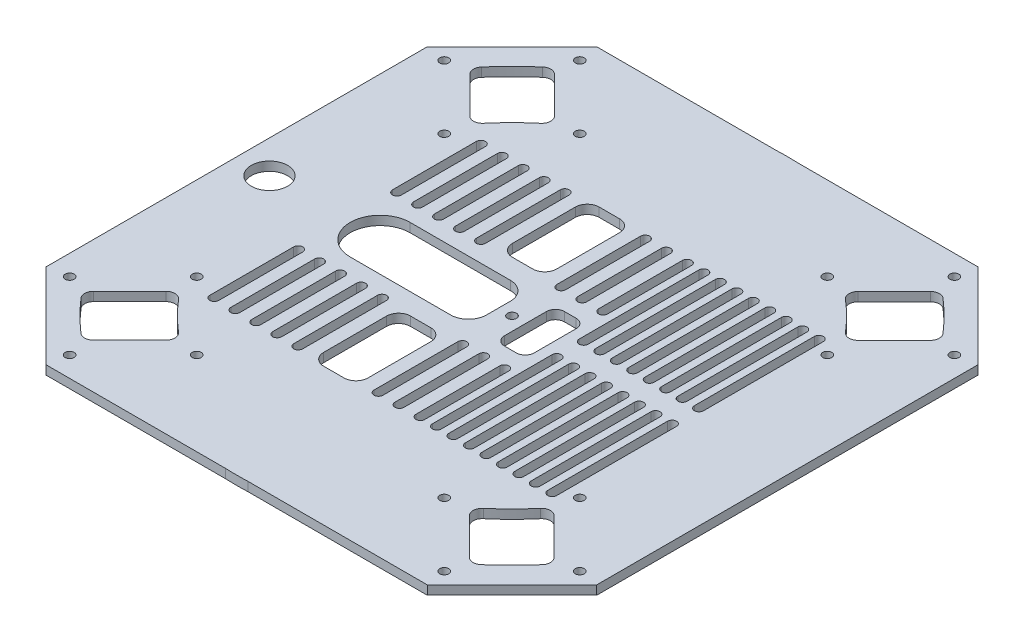
SolidWorks part; units mm, degrees
material "Thornel Mat VMA"
ref_plane "前视基准面" through (0, 0, 0) normal (0, 0, 1) x (1, 0, 0)
ref_plane "上视基准面" through (0, 0, 0) normal (0, 1, 0) x (1, 0, 0)
ref_plane "右视基准面" through (0, 0, 0) normal (1, 0, 0) x (0, 0, -1)
sketch "草图1" plane through (0, 0, 0) normal (0, 1, 0) x (1, 0, 0)
  line L0 (-63.6396, 91.9239) -> (-91.9239, 63.6396)
  line L1 (63.6396, 91.9239) -> (-63.6396, 91.9239)
  line L2 (91.9239, 63.6396) -> (91.9239, -63.6396)
  line L3 (63.6396, -91.9239) -> (-63.6396, -91.9239)
  line L4 (-91.9239, 63.6396) -> (-91.9239, -63.6396)
  line L5 (91.9239, 91.9239) -> (-91.9239, -91.9239) construction
  line L6 (91.9239, -91.9239) -> (-91.9239, 91.9239) construction
  line L7 (91.9239, -63.6396) -> (63.6396, -91.9239)
  line L8 (-91.9239, -63.6396) -> (-63.6396, -91.9239)
  line L9 (63.6396, 91.9239) -> (91.9239, 63.6396)
  line L10 (-91.9239, 91.9239) -> (-91.9239, -91.9239) construction
  line L11 (-91.9239, -91.9239) -> (91.9239, -91.9239) construction
  line L12 (91.9239, -91.9239) -> (91.9239, 91.9239) construction
  line L13 (91.9239, 91.9239) -> (-91.9239, 91.9239) construction
  point P0 (0, 0)
  dimension "D1" = 220
  dimension "D2" = 40
extrude "凸台-拉伸1" add sketch "草图1" along normal blind 3
sketch "草图15" plane through (0, 3, 0) normal (0, 1, 0) x (1, 0, 0)
  line L1 (-40.3412, 82.6837) -> (-31.9185, 62.6852)
  line L2 (44.6358, 80.4465) -> (36.2732, 60.2701)
  line L3 (-42.4295, -81.6317) -> (-34.5316, -61.2845)
  line L4 (41.391, -82.1632) -> (34.5498, -61.2743)
  arc A0 (-42.4295, -81.6317) -> (41.391, -82.1632) centre (0, 0) ccw
  arc A2 (-34.5316, -61.2845) -> (34.5498, -61.2743) centre (0, 0) ccw
  arc A3 (36.2732, 60.2701) -> (-31.9185, 62.6852) centre (0, 0) ccw
  arc A4 (44.6358, 80.4465) -> (-40.3412, 82.6837) centre (0, 0) ccw
  dimension "D1" = 92
extrude "凸台-拉伸3" add sketch "草图15" against normal up to surface (3 mm away) up to face at (0, 0, 0)
sketch "草图18" plane through (0, 3, 0) normal (0, 1, 0) x (1, 0, 0)
  line L0 (-44.0207, 0) -> (12.6253, 0) construction
  line L1 (-44.0207, 10) -> (-10.5, 10)
  line L2 (-44.0207, -10) -> (-10.5, -10)
  line L3 (-54.0207, 0) -> (-91.9239, 0) construction
  line L4 (-91.9239, 63.6396) -> (-91.9239, -63.6396) construction
  line L5 (-4.5, -10) -> (4.5, -10) construction
  line L6 (-4.5, 4) -> (-4.5, -4)
  line L9 (-4.5, 10) -> (4.5, -10) construction
  line L10 (-4.5, -10) -> (4.5, 10) construction
  line L11 (-4.5, 10) -> (4.5, 10) construction
  arc A0 (-44.0207, 10) -> (-44.0207, -10) centre (-44.0207, 0) ccw
  arc A3 (-10.5, 10) -> (-4.5, 4) centre (-10.5, 4) cw
  arc A8 (-4.5, -4) -> (-10.5, -10) centre (-10.5, -4) cw
  circle A9 centre (0, 0) radius 1.5
  point P3 (0, 0)
  point P14 (-54.0207, 0)
  point P15 (0, 0)
  dimension "D5" = 6
extrude "切除-拉伸5" cut sketch "草图18" against normal through all both and the other way through all
sketch "草图20" plane through (0, 0, 0) normal (0, -1, 0) x (1, 0, 0)
  line L0 (-45.8783, 0) -> (57.9239, 0) construction
  line L1 (57.9239, 44.5) -> (57.9239, 4.5) construction
  line L2 (59.4239, 44.5) -> (59.4239, 4.5)
  line L3 (56.4239, 44.5) -> (56.4239, 4.5)
  line L4 (57.9239, -44.5) -> (57.9239, -4.5) construction
  line L5 (59.4239, -44.5) -> (59.4239, -4.5)
  line L6 (56.4239, -44.5) -> (56.4239, -4.5)
  line L7 (52.4239, 44.5) -> (52.4239, 4.5) construction
  line L8 (53.9239, 44.5) -> (53.9239, 4.5)
  line L9 (50.9239, 44.5) -> (50.9239, 4.5)
  line L10 (52.4239, -44.5) -> (52.4239, -4.5) construction
  line L11 (53.9239, -44.5) -> (53.9239, -4.5)
  line L12 (50.9239, -44.5) -> (50.9239, -4.5)
  line L13 (46.9239, 44.5) -> (46.9239, 4.5) construction
  line L14 (48.4239, 44.5) -> (48.4239, 4.5)
  line L15 (45.4239, 44.5) -> (45.4239, 4.5)
  line L16 (46.9239, -44.5) -> (46.9239, -4.5) construction
  line L17 (48.4239, -44.5) -> (48.4239, -4.5)
  line L18 (45.4239, -44.5) -> (45.4239, -4.5)
  line L19 (41.4239, 44.5) -> (41.4239, 4.5) construction
  line L20 (42.9239, 44.5) -> (42.9239, 4.5)
  line L21 (39.9239, 44.5) -> (39.9239, 4.5)
  line L22 (41.4239, -44.5) -> (41.4239, -4.5) construction
  line L23 (42.9239, -44.5) -> (42.9239, -4.5)
  line L24 (39.9239, -44.5) -> (39.9239, -4.5)
  line L25 (35.9239, 44.5) -> (35.9239, 4.5) construction
  line L26 (37.4239, 44.5) -> (37.4239, 4.5)
  line L27 (34.4239, 44.5) -> (34.4239, 4.5)
  line L28 (35.9239, -44.5) -> (35.9239, -4.5) construction
  line L29 (37.4239, -44.5) -> (37.4239, -4.5)
  line L30 (34.4239, -44.5) -> (34.4239, -4.5)
  line L31 (30.4239, 44.5) -> (30.4239, 4.5) construction
  line L32 (31.9239, 44.5) -> (31.9239, 4.5)
  line L33 (28.9239, 44.5) -> (28.9239, 4.5)
  line L34 (30.4239, -44.5) -> (30.4239, -4.5) construction
  line L35 (31.9239, -44.5) -> (31.9239, -4.5)
  line L36 (28.9239, -44.5) -> (28.9239, -4.5)
  line L37 (24.9239, 44.5) -> (24.9239, 4.5) construction
  line L38 (26.4239, 44.5) -> (26.4239, 4.5)
  line L39 (23.4239, 44.5) -> (23.4239, 4.5)
  line L40 (24.9239, -44.5) -> (24.9239, -4.5) construction
  line L41 (26.4239, -44.5) -> (26.4239, -4.5)
  line L42 (23.4239, -44.5) -> (23.4239, -4.5)
  line L43 (19.4239, 44.5) -> (19.4239, 4.5) construction
  line L44 (20.9239, 44.5) -> (20.9239, 4.5)
  line L45 (17.9239, 44.5) -> (17.9239, 4.5)
  line L46 (19.4239, -44.5) -> (19.4239, -4.5) construction
  line L47 (20.9239, -44.5) -> (20.9239, -4.5)
  line L48 (17.9239, -44.5) -> (17.9239, -4.5)
  line L49 (91.9239, 63.6396) -> (91.9239, -63.6396) construction
  line L358 (13.9239, -44.5) -> (13.9239, -4.5) construction
  line L359 (12.4239, -44.5) -> (12.4239, -4.5) [skipped]
  line L360 (15.4239, -44.5) -> (15.4239, -4.5) [skipped]
  line L361 (13.9239, 44.5) -> (13.9239, 4.5) construction
  line L362 (15.4239, 44.5) -> (15.4239, 4.5) [skipped]
  line L363 (12.4239, 44.5) -> (12.4239, 4.5) [skipped]
  line L364 (13.9239, -44.5) -> (13.9239, -4.5) construction
  line L365 (12.4239, -44.5) -> (12.4239, -4.5) [skipped]
  line L366 (15.4239, -44.5) -> (15.4239, -4.5) [skipped]
  line L367 (13.9239, 44.5) -> (13.9239, 4.5) construction
  line L368 (15.4239, 44.5) -> (15.4239, 4.5) [skipped]
  line L369 (12.4239, 44.5) -> (12.4239, 4.5) [skipped]
  arc A0 (59.4239, 44.5) -> (56.4239, 44.5) centre (57.9239, 44.5) ccw
  arc A1 (56.4239, 4.5) -> (59.4239, 4.5) centre (57.9239, 4.5) ccw
  arc A2 (59.4239, -44.5) -> (56.4239, -44.5) centre (57.9239, -44.5) cw
  arc A3 (56.4239, -4.5) -> (59.4239, -4.5) centre (57.9239, -4.5) cw
  arc A4 (53.9239, 44.5) -> (50.9239, 44.5) centre (52.4239, 44.5) ccw
  arc A5 (50.9239, 4.5) -> (53.9239, 4.5) centre (52.4239, 4.5) ccw
  arc A6 (53.9239, -44.5) -> (50.9239, -44.5) centre (52.4239, -44.5) cw
  arc A7 (50.9239, -4.5) -> (53.9239, -4.5) centre (52.4239, -4.5) cw
  arc A8 (48.4239, 44.5) -> (45.4239, 44.5) centre (46.9239, 44.5) ccw
  arc A9 (45.4239, 4.5) -> (48.4239, 4.5) centre (46.9239, 4.5) ccw
  arc A10 (48.4239, -44.5) -> (45.4239, -44.5) centre (46.9239, -44.5) cw
  arc A11 (45.4239, -4.5) -> (48.4239, -4.5) centre (46.9239, -4.5) cw
  arc A12 (42.9239, 44.5) -> (39.9239, 44.5) centre (41.4239, 44.5) ccw
  arc A13 (39.9239, 4.5) -> (42.9239, 4.5) centre (41.4239, 4.5) ccw
  arc A14 (42.9239, -44.5) -> (39.9239, -44.5) centre (41.4239, -44.5) cw
  arc A15 (39.9239, -4.5) -> (42.9239, -4.5) centre (41.4239, -4.5) cw
  arc A16 (37.4239, 44.5) -> (34.4239, 44.5) centre (35.9239, 44.5) ccw
  arc A17 (34.4239, 4.5) -> (37.4239, 4.5) centre (35.9239, 4.5) ccw
  arc A18 (37.4239, -44.5) -> (34.4239, -44.5) centre (35.9239, -44.5) cw
  arc A19 (34.4239, -4.5) -> (37.4239, -4.5) centre (35.9239, -4.5) cw
  arc A20 (31.9239, 44.5) -> (28.9239, 44.5) centre (30.4239, 44.5) ccw
  arc A21 (28.9239, 4.5) -> (31.9239, 4.5) centre (30.4239, 4.5) ccw
  arc A22 (31.9239, -44.5) -> (28.9239, -44.5) centre (30.4239, -44.5) cw
  arc A23 (28.9239, -4.5) -> (31.9239, -4.5) centre (30.4239, -4.5) cw
  arc A24 (26.4239, 44.5) -> (23.4239, 44.5) centre (24.9239, 44.5) ccw
  arc A25 (23.4239, 4.5) -> (26.4239, 4.5) centre (24.9239, 4.5) ccw
  arc A26 (26.4239, -44.5) -> (23.4239, -44.5) centre (24.9239, -44.5) cw
  arc A27 (23.4239, -4.5) -> (26.4239, -4.5) centre (24.9239, -4.5) cw
  arc A28 (20.9239, 44.5) -> (17.9239, 44.5) centre (19.4239, 44.5) ccw
  arc A29 (17.9239, 4.5) -> (20.9239, 4.5) centre (19.4239, 4.5) ccw
  arc A30 (20.9239, -44.5) -> (17.9239, -44.5) centre (19.4239, -44.5) cw
  arc A31 (17.9239, -4.5) -> (20.9239, -4.5) centre (19.4239, -4.5) cw
  arc A242 (12.4239, -44.5) -> (15.4239, -44.5) centre (13.9239, -44.5) ccw [skipped]
  arc A243 (15.4239, -4.5) -> (12.4239, -4.5) centre (13.9239, -4.5) ccw [skipped]
  arc A244 (15.4239, 44.5) -> (12.4239, 44.5) centre (13.9239, 44.5) ccw [skipped]
  arc A245 (12.4239, 4.5) -> (15.4239, 4.5) centre (13.9239, 4.5) ccw [skipped]
  point P5 (57.9239, 24.5)
  point P11 (57.9239, 3)
  point P13 (57.9239, -24.5)
  point P18 (57.9239, -3)
  point P19 (79.1207, 0)
  point P23 (52.4239, 24.5)
  point P29 (52.4239, 3)
  point P31 (52.4239, -24.5)
  point P36 (52.4239, -3)
  point P39 (46.9239, 24.5)
  point P45 (46.9239, 3)
  point P47 (46.9239, -24.5)
  point P52 (46.9239, -3)
  point P55 (41.4239, 24.5)
  point P61 (41.4239, 3)
  point P63 (41.4239, -24.5)
  point P68 (41.4239, -3)
  point P71 (35.9239, 24.5)
  point P77 (35.9239, 3)
  point P79 (35.9239, -24.5)
  point P84 (35.9239, -3)
  point P87 (30.4239, 24.5)
  point P93 (30.4239, 3)
  point P95 (30.4239, -24.5)
  point P100 (30.4239, -3)
  point P103 (24.9239, 24.5)
  point P109 (24.9239, 3)
  point P111 (24.9239, -24.5)
  point P116 (24.9239, -3)
  point P119 (19.4239, 24.5)
  point P125 (19.4239, 3)
  point P127 (19.4239, -24.5)
  point P132 (19.4239, -3)
  point P135 (21.0655, -24.0622)
  point P140 (13.9239, -3)
  point P142 (13.9239, 3)
  point P149 (21.0655, 24.0622)
  point P157 (21.0655, -24.0622)
  point P164 (21.0655, 24.0622)
  point P171 (21.0655, -24.0622)
  point P178 (21.0655, 24.0622)
  point P185 (21.0655, -24.0622)
  point P192 (21.0655, 24.0622)
  point P199 (21.0655, -24.0622)
  point P206 (21.0655, 24.0622)
  point P213 (21.0655, -24.0622)
  point P220 (21.0655, 24.0622)
  point P227 (16.1207, -24.0622)
  point P234 (16.1207, 24.0622)
  point P241 (16.1207, -24.0622)
  point P248 (16.1207, 24.0622)
  point P255 (11.1207, -24.0622)
  point P262 (11.1207, 24.0622)
  point P269 (11.1207, -24.0622)
  point P276 (11.1207, 24.0622)
  point P283 (11.1207, -29.0622)
  point P290 (11.1207, 29.0622)
  point P297 (11.1207, -29.0622)
  point P304 (11.1207, 29.0622)
  point P311 (15.1207, -29)
  point P318 (15.1207, 29)
  point P325 (15.1207, -29)
  point P332 (15.1207, 29)
  point P339 (15.1207, -24)
  point P346 (15.1207, 24)
  point P353 (15.1207, -24)
  point P360 (15.1207, 24)
  point P367 (15.1207, -24.5)
  point P374 (15.1207, 24.5)
  point P381 (15.1207, -24.5)
  point P388 (15.1207, 24.5)
  point P395 (15.1207, -24.5)
  point P402 (15.1207, 24.5)
  point P409 (15.1207, -24.5)
  point P416 (15.1207, 24.5)
  point P423 (15.1207, -24.5)
  point P430 (15.1207, 24.5)
  point P437 (15.1207, -24.5)
  point P444 (15.1207, 24.5)
  point P451 (15.1207, -24.5)
  point P458 (15.1207, 24.5)
  point P465 (15.1207, -24.5)
  point P472 (15.1207, 24.5)
  point P479 (15.1207, -24.5)
  point P486 (15.1207, 24.5)
  point P493 (15.1207, -24.5)
  point P500 (15.1207, 24.5)
  point P507 (15.1207, -24.5)
  point P514 (15.1207, 24.5)
  point P521 (15.1207, -24.5)
  point P528 (15.1207, 24.5)
  point P535 (15.1207, -24.5)
  point P542 (15.1207, 24.5)
  point P549 (15.1207, -24.5)
  point P556 (15.1207, 24.5)
  point P563 (15.1207, -24.5)
  point P570 (15.1207, 24.5)
  point P577 (15.1207, -24.5)
  point P584 (15.1207, 24.5)
  point P591 (15.1207, -24.5)
  point P598 (15.1207, 24.5)
  point P605 (15.1207, -24.5)
  point P612 (15.1207, 24.5)
  point P619 (15.1207, -24.5)
  point P626 (15.1207, 24.5)
  point P633 (15.1207, -24.5)
  point P640 (15.1207, 24.5)
  point P647 (15.1207, -24.5)
  point P654 (15.1207, 24.5)
  point P661 (15.1207, -24.5)
  point P668 (15.1207, 24.5)
  point P675 (15.1207, -24.5)
  point P682 (15.1207, 24.5)
  point P689 (15.1207, -24.5)
  point P696 (15.1207, 24.5)
  point P703 (15.1207, -24.5)
  point P710 (15.1207, 24.5)
  point P717 (15.1207, -24.5)
  point P724 (15.1207, 24.5)
  point P731 (15.1207, -24.5)
  point P738 (15.1207, 24.5)
  point P745 (15.1207, -24.5)
  point P752 (15.1207, 24.5)
  point P759 (15.1207, -24.5)
  point P766 (15.1207, 24.5)
  point P773 (15.1207, -24.5)
  point P780 (15.1207, 24.5)
  point P787 (15.1207, -24.5)
  point P794 (15.1207, 24.5)
  point P801 (15.1207, -24.5)
  point P808 (15.1207, 24.5)
  point P815 (14.4239, -24.5)
  point P822 (14.4239, 24.5)
  point P829 (14.4239, -24.5)
  point P836 (14.4239, 24.5)
  point P843 (13.9239, -24.5)
  point P850 (13.9239, 24.5)
  point P857 (13.9239, -24.5)
  point P864 (13.9239, 24.5)
  point P871 (13.9239, -24.5)
  point P878 (13.9239, 24.5)
  dimension "D2" = 9
  dimension "D5" = 1.5
  dimension "D1" = 3
  dimension "D3" = 40
  dimension "D4" = 34
  dimension "D6" = 5.5
extrude "切除-拉伸7" cut sketch "草图20" against normal through all both and the other way through all
sketch "草图21" plane through (0, 3, 0) normal (0, 1, 0) x (1, 0, 0)
  line L0 (13.9239, 16.5) -> (13.9239, 44.5) construction
  line L1 (12.4239, 16.5) -> (12.4239, 44.5)
  line L2 (15.4239, 16.5) -> (15.4239, 44.5)
  line L3 (13.9239, 44.5) -> (19.4239, 44.5) construction
  line L4 (17.9239, 4.5) -> (17.9239, 44.5) construction
  line L5 (-13.3448, 10) -> (17.9239, 10) construction
  line L6 (-10.5, 10) -> (-44.0207, 10) construction
  line L7 (0, 0) -> (29.0659, 0) construction
  line L8 (13.9239, -16.5) -> (13.9239, -44.5) construction
  line L9 (15.4239, -16.5) -> (15.4239, -44.5)
  line L10 (12.4239, -16.5) -> (12.4239, -44.5)
  line L12 (6.9239, 44.5) -> (12.4239, 44.5) construction
  line L14 (6.9239, 16.5) -> (6.9239, 44.5) construction
  line L15 (5.4239, 16.5) -> (5.4239, 44.5)
  line L16 (8.4239, 16.5) -> (8.4239, 44.5)
  line L17 (6.9239, -16.5) -> (6.9239, -44.5) construction
  line L18 (8.4239, -16.5) -> (8.4239, -44.5)
  line L19 (5.4239, -16.5) -> (5.4239, -44.5)
  line L20 (-0.0761, 44.5) -> (5.4239, 44.5) construction
  line L21 (6.6207, -44.5) -> (1.1207, -44.5) construction
  line L22 (-0.0761, 16.5) -> (-0.0761, 44.5) construction
  line L23 (-1.5761, 16.5) -> (-1.5761, 44.5)
  line L24 (1.4239, 16.5) -> (1.4239, 44.5)
  line L25 (-0.0761, -16.5) -> (-0.0761, -44.5) construction
  line L26 (1.4239, -16.5) -> (1.4239, -44.5)
  line L27 (-1.5761, -16.5) -> (-1.5761, -44.5)
  line L28 (-7.0761, 44.5) -> (-1.5761, 44.5) construction
  line L29 (-0.3793, -44.5) -> (-5.8793, -44.5) construction
  line L52 (-28.0761, 44.5) -> (-22.5761, 44.5) construction
  line L53 (-21.3793, -44.5) -> (-26.8793, -44.5) construction
  line L54 (-35.0761, 44.5) -> (-29.5761, 44.5) construction
  line L55 (-28.3793, -44.5) -> (-33.8793, -44.5) construction
  line L56 (-7, 0) -> (22.0659, 0) construction
  line L57 (-26.8793, 16.5) -> (-26.8793, 44.5) construction
  line L58 (-28.3793, 16.5) -> (-28.3793, 44.5)
  line L59 (-25.3793, 16.5) -> (-25.3793, 44.5)
  line L60 (-26.8793, -16.5) -> (-26.8793, -44.5) construction
  line L61 (-25.3793, -16.5) -> (-25.3793, -44.5)
  line L62 (-28.3793, -16.5) -> (-28.3793, -44.5)
  line L63 (-42.0761, 44.5) -> (-36.5761, 44.5) construction
  line L64 (-35.3793, -44.5) -> (-40.8793, -44.5) construction
  line L65 (-14, 0) -> (15.0659, 0) construction
  line L66 (-33.8793, 16.5) -> (-33.8793, 44.5) construction
  line L67 (-35.3793, 16.5) -> (-35.3793, 44.5)
  line L68 (-32.3793, 16.5) -> (-32.3793, 44.5)
  line L69 (-33.8793, -16.5) -> (-33.8793, -44.5) construction
  line L70 (-32.3793, -16.5) -> (-32.3793, -44.5)
  line L71 (-35.3793, -16.5) -> (-35.3793, -44.5)
  line L72 (-49.0761, 44.5) -> (-43.5761, 44.5) construction
  line L73 (-42.3793, -44.5) -> (-47.8793, -44.5) construction
  line L74 (-21, 0) -> (8.0659, 0) construction
  line L75 (-40.8793, 16.5) -> (-40.8793, 44.5) construction
  line L76 (-42.3793, 16.5) -> (-42.3793, 44.5)
  line L77 (-39.3793, 16.5) -> (-39.3793, 44.5)
  line L78 (-40.8793, -16.5) -> (-40.8793, -44.5) construction
  line L79 (-39.3793, -16.5) -> (-39.3793, -44.5)
  line L80 (-42.3793, -16.5) -> (-42.3793, -44.5)
  line L81 (-56.0761, 44.5) -> (-50.5761, 44.5) construction
  line L82 (-49.3793, -44.5) -> (-54.8793, -44.5) construction
  line L83 (-28, 0) -> (1.0659, 0) construction
  line L84 (-47.8793, 16.5) -> (-47.8793, 44.5) construction
  line L85 (-49.3793, 16.5) -> (-49.3793, 44.5)
  line L86 (-46.3793, 16.5) -> (-46.3793, 44.5)
  line L87 (-47.8793, -16.5) -> (-47.8793, -44.5) construction
  line L88 (-46.3793, -16.5) -> (-46.3793, -44.5)
  line L89 (-49.3793, -16.5) -> (-49.3793, -44.5)
  line L90 (-63.0761, 44.5) -> (-57.5761, 44.5) construction
  line L91 (-56.3793, -44.5) -> (-61.8793, -44.5) construction
  line L92 (-35, 0) -> (-5.9341, 0) construction
  line L93 (-54.8793, 16.5) -> (-54.8793, 44.5) construction
  line L94 (-56.3793, 16.5) -> (-56.3793, 44.5)
  line L95 (-35.0761, 44.5) -> (-29.5761, 44.5) construction
  line L97 (-42.0761, 44.5) -> (-36.5761, 44.5) construction
  line L99 (-49.0761, 44.5) -> (-43.5761, 44.5) construction
  line L101 (-56.0761, 44.5) -> (-50.5761, 44.5) construction
  line L163 (-53.3793, 16.5) -> (-53.3793, 44.5)
  line L164 (-54.8793, -16.5) -> (-54.8793, -44.5) construction
  line L165 (-53.3793, -16.5) -> (-53.3793, -44.5)
  line L166 (-56.3793, -16.5) -> (-56.3793, -44.5)
  line L227 (-14.0761, 44.5) -> (-8.5761, 44.5) construction
  line L229 (-21.0761, 44.5) -> (-15.5761, 44.5) construction
  line L1960 (-6.5761, -16.5) -> (-6.5761, -44.5) construction
  line L1961 (-5.0761, -16.5) -> (-5.0761, -44.5) [skipped]
  line L1962 (-8.0761, -16.5) -> (-8.0761, -44.5) [skipped]
  line L1963 (-13.5761, 16.5) -> (-13.5761, 44.5) construction
  line L1964 (-15.0761, 16.5) -> (-15.0761, 44.5) [skipped]
  line L1965 (-12.0761, 16.5) -> (-12.0761, 44.5) [skipped]
  line L1966 (-13.5761, -16.5) -> (-13.5761, -44.5) construction
  line L1967 (-12.0761, -16.5) -> (-12.0761, -44.5) [skipped]
  line L1968 (-15.0761, -16.5) -> (-15.0761, -44.5) [skipped]
  line L1969 (-20.5761, 16.5) -> (-20.5761, 44.5) construction
  line L1970 (-22.0761, 16.5) -> (-22.0761, 44.5) [skipped]
  line L1971 (-19.0761, 16.5) -> (-19.0761, 44.5) [skipped]
  line L1972 (-20.5761, -16.5) -> (-20.5761, -44.5) construction
  line L1973 (-19.0761, -16.5) -> (-19.0761, -44.5) [skipped]
  line L1974 (-22.0761, -16.5) -> (-22.0761, -44.5) [skipped]
  line L1975 (-6.5761, 16.5) -> (-6.5761, 44.5) construction
  line L1976 (-8.0761, 16.5) -> (-8.0761, 44.5) [skipped]
  line L1977 (-5.0761, 16.5) -> (-5.0761, 44.5) [skipped]
  line L1978 (-27.5761, -16.5) -> (-27.5761, -44.5) construction
  line L1979 (-26.0761, -16.5) -> (-26.0761, -44.5) [skipped]
  line L1980 (-29.0761, -16.5) -> (-29.0761, -44.5) [skipped]
  line L1981 (-34.5761, 16.5) -> (-34.5761, 44.5) construction
  line L1982 (-36.0761, 16.5) -> (-36.0761, 44.5) [skipped]
  line L1983 (-33.0761, 16.5) -> (-33.0761, 44.5) [skipped]
  line L1984 (-34.5761, -16.5) -> (-34.5761, -44.5) construction
  line L1985 (-33.0761, -16.5) -> (-33.0761, -44.5) [skipped]
  line L1986 (-36.0761, -16.5) -> (-36.0761, -44.5) [skipped]
  line L1987 (-41.5761, 16.5) -> (-41.5761, 44.5) construction
  line L1988 (-43.0761, 16.5) -> (-43.0761, 44.5) [skipped]
  line L1989 (-40.0761, 16.5) -> (-40.0761, 44.5) [skipped]
  line L1990 (-41.5761, -16.5) -> (-41.5761, -44.5) construction
  line L1991 (-40.0761, -16.5) -> (-40.0761, -44.5) [skipped]
  line L1992 (-43.0761, -16.5) -> (-43.0761, -44.5) [skipped]
  line L1993 (-48.5761, 16.5) -> (-48.5761, 44.5) construction
  line L1994 (-50.0761, 16.5) -> (-50.0761, 44.5) [skipped]
  line L1995 (-47.0761, 16.5) -> (-47.0761, 44.5) [skipped]
  line L1996 (-48.5761, -16.5) -> (-48.5761, -44.5) construction
  line L1997 (-47.0761, -16.5) -> (-47.0761, -44.5) [skipped]
  line L1998 (-50.0761, -16.5) -> (-50.0761, -44.5) [skipped]
  line L1999 (-55.5761, 16.5) -> (-55.5761, 44.5) construction
  line L2000 (-57.0761, 16.5) -> (-57.0761, 44.5) [skipped]
  line L2001 (-54.0761, 16.5) -> (-54.0761, 44.5) [skipped]
  line L2002 (-55.5761, -16.5) -> (-55.5761, -44.5) construction
  line L2003 (-54.0761, -16.5) -> (-54.0761, -44.5) [skipped]
  line L2004 (-57.0761, -16.5) -> (-57.0761, -44.5) [skipped]
  line L2005 (-27.5761, 16.5) -> (-27.5761, 44.5) construction
  line L2006 (-29.0761, 16.5) -> (-29.0761, 44.5) [skipped]
  line L2007 (-26.0761, 16.5) -> (-26.0761, 44.5) [skipped]
  line L2008 (-7.0761, -16.5) -> (-7.0761, -44.5) construction
  line L2009 (-5.5761, -16.5) -> (-5.5761, -44.5) [skipped]
  line L2010 (-8.5761, -16.5) -> (-8.5761, -44.5) [skipped]
  line L2011 (-14.0761, 16.5) -> (-14.0761, 44.5) construction
  line L2012 (-15.5761, 16.5) -> (-15.5761, 44.5) [skipped]
  line L2013 (-12.5761, 16.5) -> (-12.5761, 44.5) [skipped]
  line L2014 (-14.0761, -16.5) -> (-14.0761, -44.5) construction
  line L2015 (-12.5761, -16.5) -> (-12.5761, -44.5) [skipped]
  line L2016 (-15.5761, -16.5) -> (-15.5761, -44.5) [skipped]
  line L2017 (-21.0761, 16.5) -> (-21.0761, 44.5) construction
  line L2018 (-22.5761, 16.5) -> (-22.5761, 44.5) [skipped]
  line L2019 (-19.5761, 16.5) -> (-19.5761, 44.5) [skipped]
  line L2020 (-21.0761, -16.5) -> (-21.0761, -44.5) construction
  line L2021 (-19.5761, -16.5) -> (-19.5761, -44.5) [skipped]
  line L2022 (-22.5761, -16.5) -> (-22.5761, -44.5) [skipped]
  line L2023 (-7.0761, 16.5) -> (-7.0761, 44.5) construction
  line L2024 (-8.5761, 16.5) -> (-8.5761, 44.5) [skipped]
  line L2025 (-5.5761, 16.5) -> (-5.5761, 44.5) [skipped]
  line L2026 (-28.0761, -16.5) -> (-28.0761, -44.5) construction
  line L2027 (-26.5761, -16.5) -> (-26.5761, -44.5) [skipped]
  line L2028 (-29.5761, -16.5) -> (-29.5761, -44.5) [skipped]
  line L2029 (-35.0761, 16.5) -> (-35.0761, 44.5) construction
  line L2030 (-36.5761, 16.5) -> (-36.5761, 44.5) [skipped]
  line L2031 (-33.5761, 16.5) -> (-33.5761, 44.5) [skipped]
  line L2032 (-35.0761, -16.5) -> (-35.0761, -44.5) construction
  line L2033 (-33.5761, -16.5) -> (-33.5761, -44.5) [skipped]
  line L2034 (-36.5761, -16.5) -> (-36.5761, -44.5) [skipped]
  line L2035 (-42.0761, 16.5) -> (-42.0761, 44.5) construction
  line L2036 (-43.5761, 16.5) -> (-43.5761, 44.5) [skipped]
  line L2037 (-40.5761, 16.5) -> (-40.5761, 44.5) [skipped]
  line L2038 (-42.0761, -16.5) -> (-42.0761, -44.5) construction
  line L2039 (-40.5761, -16.5) -> (-40.5761, -44.5) [skipped]
  line L2040 (-43.5761, -16.5) -> (-43.5761, -44.5) [skipped]
  line L2041 (-49.0761, 16.5) -> (-49.0761, 44.5) construction
  line L2042 (-50.5761, 16.5) -> (-50.5761, 44.5) [skipped]
  line L2043 (-47.5761, 16.5) -> (-47.5761, 44.5) [skipped]
  line L2044 (-49.0761, -16.5) -> (-49.0761, -44.5) construction
  line L2045 (-47.5761, -16.5) -> (-47.5761, -44.5) [skipped]
  line L2046 (-50.5761, -16.5) -> (-50.5761, -44.5) [skipped]
  line L2047 (-56.0761, 16.5) -> (-56.0761, 44.5) construction
  line L2048 (-57.5761, 16.5) -> (-57.5761, 44.5) [skipped]
  line L2049 (-54.5761, 16.5) -> (-54.5761, 44.5) [skipped]
  line L2050 (-56.0761, -16.5) -> (-56.0761, -44.5) construction
  line L2051 (-54.5761, -16.5) -> (-54.5761, -44.5) [skipped]
  line L2052 (-57.5761, -16.5) -> (-57.5761, -44.5) [skipped]
  line L2053 (-28.0761, 16.5) -> (-28.0761, 44.5) construction
  line L2054 (-29.5761, 16.5) -> (-29.5761, 44.5) [skipped]
  line L2055 (-26.5761, 16.5) -> (-26.5761, 44.5) [skipped]
  arc A0 (12.4239, 16.5) -> (15.4239, 16.5) centre (13.9239, 16.5) ccw
  arc A1 (15.4239, 44.5) -> (12.4239, 44.5) centre (13.9239, 44.5) ccw
  arc A2 (15.4239, -16.5) -> (12.4239, -16.5) centre (13.9239, -16.5) ccw
  arc A3 (12.4239, -44.5) -> (15.4239, -44.5) centre (13.9239, -44.5) ccw
  arc A5 (17.9239, -44.5) -> (20.9239, -44.5) centre (19.4239, -44.5) ccw construction
  arc A6 (5.4239, 16.5) -> (8.4239, 16.5) centre (6.9239, 16.5) ccw
  arc A7 (8.4239, 44.5) -> (5.4239, 44.5) centre (6.9239, 44.5) ccw
  arc A8 (8.4239, -16.5) -> (5.4239, -16.5) centre (6.9239, -16.5) ccw
  arc A9 (5.4239, -44.5) -> (8.4239, -44.5) centre (6.9239, -44.5) ccw
  arc A10 (-1.5761, 16.5) -> (1.4239, 16.5) centre (-0.0761, 16.5) ccw
  arc A11 (1.4239, 44.5) -> (-1.5761, 44.5) centre (-0.0761, 44.5) ccw
  arc A12 (1.4239, -16.5) -> (-1.5761, -16.5) centre (-0.0761, -16.5) ccw
  arc A13 (-1.5761, -44.5) -> (1.4239, -44.5) centre (-0.0761, -44.5) ccw
  arc A26 (-28.3793, 16.5) -> (-25.3793, 16.5) centre (-26.8793, 16.5) ccw
  arc A27 (-25.3793, 44.5) -> (-28.3793, 44.5) centre (-26.8793, 44.5) ccw
  arc A28 (-25.3793, -16.5) -> (-28.3793, -16.5) centre (-26.8793, -16.5) ccw
  arc A29 (-28.3793, -44.5) -> (-25.3793, -44.5) centre (-26.8793, -44.5) ccw
  arc A30 (-35.3793, 16.5) -> (-32.3793, 16.5) centre (-33.8793, 16.5) ccw
  arc A31 (-32.3793, 44.5) -> (-35.3793, 44.5) centre (-33.8793, 44.5) ccw
  arc A32 (-32.3793, -16.5) -> (-35.3793, -16.5) centre (-33.8793, -16.5) ccw
  arc A33 (-35.3793, -44.5) -> (-32.3793, -44.5) centre (-33.8793, -44.5) ccw
  arc A34 (-42.3793, 16.5) -> (-39.3793, 16.5) centre (-40.8793, 16.5) ccw
  arc A35 (-39.3793, 44.5) -> (-42.3793, 44.5) centre (-40.8793, 44.5) ccw
  arc A36 (-39.3793, -16.5) -> (-42.3793, -16.5) centre (-40.8793, -16.5) ccw
  arc A37 (-42.3793, -44.5) -> (-39.3793, -44.5) centre (-40.8793, -44.5) ccw
  arc A38 (-49.3793, 16.5) -> (-46.3793, 16.5) centre (-47.8793, 16.5) ccw
  arc A39 (-46.3793, 44.5) -> (-49.3793, 44.5) centre (-47.8793, 44.5) ccw
  arc A40 (-46.3793, -16.5) -> (-49.3793, -16.5) centre (-47.8793, -16.5) ccw
  arc A41 (-49.3793, -44.5) -> (-46.3793, -44.5) centre (-47.8793, -44.5) ccw
  arc A42 (-56.3793, 16.5) -> (-53.3793, 16.5) centre (-54.8793, 16.5) ccw
  arc A43 (-53.3793, 44.5) -> (-56.3793, 44.5) centre (-54.8793, 44.5) ccw
  arc A44 (-53.3793, -16.5) -> (-56.3793, -16.5) centre (-54.8793, -16.5) ccw
  arc A45 (-56.3793, -44.5) -> (-53.3793, -44.5) centre (-54.8793, -44.5) ccw
  arc A1312 (-5.5761, -16.5) -> (-8.5761, -16.5) centre (-7.0761, -16.5) ccw [skipped]
  arc A1313 (-8.5761, -44.5) -> (-5.5761, -44.5) centre (-7.0761, -44.5) ccw [skipped]
  arc A1314 (-15.5761, 16.5) -> (-12.5761, 16.5) centre (-14.0761, 16.5) ccw [skipped]
  arc A1315 (-12.5761, 44.5) -> (-15.5761, 44.5) centre (-14.0761, 44.5) ccw [skipped]
  arc A1316 (-12.5761, -16.5) -> (-15.5761, -16.5) centre (-14.0761, -16.5) ccw [skipped]
  arc A1317 (-15.5761, -44.5) -> (-12.5761, -44.5) centre (-14.0761, -44.5) ccw [skipped]
  arc A1318 (-22.5761, 16.5) -> (-19.5761, 16.5) centre (-21.0761, 16.5) ccw [skipped]
  arc A1319 (-19.5761, 44.5) -> (-22.5761, 44.5) centre (-21.0761, 44.5) ccw [skipped]
  arc A1320 (-19.5761, -16.5) -> (-22.5761, -16.5) centre (-21.0761, -16.5) ccw [skipped]
  arc A1321 (-22.5761, -44.5) -> (-19.5761, -44.5) centre (-21.0761, -44.5) ccw [skipped]
  arc A1322 (-8.5761, 16.5) -> (-5.5761, 16.5) centre (-7.0761, 16.5) ccw [skipped]
  arc A1323 (-5.5761, 44.5) -> (-8.5761, 44.5) centre (-7.0761, 44.5) ccw [skipped]
  arc A1324 (-26.5761, -16.5) -> (-29.5761, -16.5) centre (-28.0761, -16.5) ccw [skipped]
  arc A1325 (-29.5761, -44.5) -> (-26.5761, -44.5) centre (-28.0761, -44.5) ccw [skipped]
  arc A1326 (-36.5761, 16.5) -> (-33.5761, 16.5) centre (-35.0761, 16.5) ccw [skipped]
  arc A1327 (-33.5761, 44.5) -> (-36.5761, 44.5) centre (-35.0761, 44.5) ccw [skipped]
  arc A1328 (-33.5761, -16.5) -> (-36.5761, -16.5) centre (-35.0761, -16.5) ccw [skipped]
  arc A1329 (-36.5761, -44.5) -> (-33.5761, -44.5) centre (-35.0761, -44.5) ccw [skipped]
  arc A1330 (-43.5761, 16.5) -> (-40.5761, 16.5) centre (-42.0761, 16.5) ccw [skipped]
  arc A1331 (-40.5761, 44.5) -> (-43.5761, 44.5) centre (-42.0761, 44.5) ccw [skipped]
  arc A1332 (-40.5761, -16.5) -> (-43.5761, -16.5) centre (-42.0761, -16.5) ccw [skipped]
  arc A1333 (-43.5761, -44.5) -> (-40.5761, -44.5) centre (-42.0761, -44.5) ccw [skipped]
  arc A1334 (-50.5761, 16.5) -> (-47.5761, 16.5) centre (-49.0761, 16.5) ccw [skipped]
  arc A1335 (-47.5761, 44.5) -> (-50.5761, 44.5) centre (-49.0761, 44.5) ccw [skipped]
  arc A1336 (-47.5761, -16.5) -> (-50.5761, -16.5) centre (-49.0761, -16.5) ccw [skipped]
  arc A1337 (-50.5761, -44.5) -> (-47.5761, -44.5) centre (-49.0761, -44.5) ccw [skipped]
  arc A1338 (-57.5761, 16.5) -> (-54.5761, 16.5) centre (-56.0761, 16.5) ccw [skipped]
  arc A1339 (-54.5761, 44.5) -> (-57.5761, 44.5) centre (-56.0761, 44.5) ccw [skipped]
  arc A1340 (-54.5761, -16.5) -> (-57.5761, -16.5) centre (-56.0761, -16.5) ccw [skipped]
  arc A1341 (-57.5761, -44.5) -> (-54.5761, -44.5) centre (-56.0761, -44.5) ccw [skipped]
  arc A1342 (-29.5761, 16.5) -> (-26.5761, 16.5) centre (-28.0761, 16.5) ccw [skipped]
  arc A1343 (-26.5761, 44.5) -> (-29.5761, 44.5) centre (-28.0761, 44.5) ccw [skipped]
  point P2 (13.9239, 30.5)
  point P7 (19.4239, 44.5)
  point P13 (13.9239, 15)
  point P23 (13.9239, -30.5)
  point P37 (6.9239, 30.5)
  point P42 (12.4239, 44.5)
  point P45 (6.9239, 15)
  point P47 (6.9239, -30.5)
  point P56 (-0.0761, 30.5)
  point P61 (5.4239, 44.5)
  point P64 (-0.0761, 15)
  point P66 (-0.0761, -30.5)
  point P76 (-5.8793, -30.5)
  point P80 (-1.5761, 44.5)
  point P85 (-12.8793, 30.5)
  point P93 (-22.5761, 44.5)
  point P95 (-12.8793, -30.5)
  point P99 (-7.0761, 15)
  point P101 (-21.0761, 15)
  point P102 (-8.5761, 44.5)
  point P104 (-19.8793, 30.5)
  point P109 (-15.5761, 44.5)
  point P110 (-14.0761, 15)
  point P114 (-19.8793, -30.5)
  point P133 (-26.8793, -30.5)
  point P136 (-26.8793, 30.5)
  point P142 (-33.8793, 30.5)
  point P145 (-26.8793, 15)
  point P149 (-26.8793, -30.5)
  point P150 (-56.0761, 15)
  point P152 (-33.8793, -30.5)
  point P156 (-28.0761, 15)
  point P158 (-50.5761, 44.5)
  point P159 (-29.5761, 44.5)
  point P160 (-28.3793, 44.5)
  point P161 (-40.8793, 30.5)
  point P166 (-49.0761, 15)
  point P167 (-43.5761, 44.5)
  point P169 (-42.0761, 15)
  point P171 (-40.8793, -30.5)
  point P173 (-33.8793, 30.5)
  point P175 (-35.0761, 15)
  point P177 (-36.5761, 44.5)
  point P180 (-47.8793, 30.5)
  point P182 (-33.8793, 15)
  point P184 (-33.8793, -30.5)
  point P190 (-47.8793, -30.5)
  point P191 (-35.3793, 44.5)
  point P199 (-54.8793, 30.5)
  point P200 (-40.8793, 30.5)
  point P206 (-40.8793, 15)
  point P208 (-40.8793, -30.5)
  point P209 (-54.8793, -30.5)
  point P215 (-42.3793, 44.5)
  point P223 (-47.8793, 30.5)
  point P225 (-26.8793, 30.5)
  point P230 (-47.8793, 15)
  point P232 (-47.8793, -30.5)
  point P251 (-5.8793, 30.5)
  point P253 (-26.8793, -30.5)
  point P260 (-33.8793, 30.5)
  point P267 (-33.8793, -30.5)
  point P274 (-40.8793, 30.5)
  point P281 (-40.8793, -30.5)
  point P288 (-47.8793, 30.5)
  point P295 (-47.8793, -30.5)
  point P302 (-54.8793, 30.5)
  point P309 (-54.8793, -30.5)
  point P316 (-26.8793, 30.5)
  point P323 (-26.8793, -30.5)
  point P330 (-33.8793, 30.5)
  point P337 (-33.8793, -30.5)
  point P344 (-40.8793, 30.5)
  point P351 (-40.8793, -30.5)
  point P358 (-47.8793, 30.5)
  point P365 (-47.8793, -30.5)
  point P372 (-54.8793, 30.5)
  point P379 (-54.8793, -30.5)
  point P386 (-26.8793, 30.5)
  point P394 (-49.3793, 44.5)
  point P402 (-54.8793, 30.5)
  point P408 (-54.8793, 15)
  point P410 (-54.8793, -30.5)
  point P416 (-56.3793, 44.5)
  point P422 (-26.8793, -30.5)
  point P429 (-33.8793, 30.5)
  point P436 (-33.8793, -30.5)
  point P443 (-40.8793, 30.5)
  point P450 (-40.8793, -30.5)
  point P457 (-47.8793, 30.5)
  point P464 (-47.8793, -30.5)
  point P471 (-54.8793, 30.5)
  point P478 (-54.8793, -30.5)
  point P485 (-26.8793, 30.5)
  point P492 (-26.8793, -30.5)
  point P499 (-33.8793, 30.5)
  point P506 (-33.8793, -30.5)
  point P513 (-40.8793, 30.5)
  point P520 (-40.8793, -30.5)
  point P527 (-47.8793, 30.5)
  point P534 (-47.8793, -30.5)
  point P541 (-54.8793, 30.5)
  point P548 (-54.8793, -30.5)
  point P555 (-26.8793, 30.5)
  point P572 (-5.8793, -30.5)
  point P579 (-12.8793, 30.5)
  point P586 (-12.8793, -30.5)
  point P593 (-19.8793, 30.5)
  point P600 (-19.8793, -30.5)
  point P607 (-5.8793, 30.5)
  point P614 (-26.8793, -30.5)
  point P621 (-33.8793, 30.5)
  point P628 (-33.8793, -30.5)
  point P635 (-40.8793, 30.5)
  point P642 (-40.8793, -30.5)
  point P649 (-47.8793, 30.5)
  point P656 (-47.8793, -30.5)
  point P663 (-54.8793, 30.5)
  point P670 (-54.8793, -30.5)
  point P677 (-26.8793, 30.5)
  point P684 (-5.8793, -30.5)
  point P691 (-12.8793, 30.5)
  point P698 (-12.8793, -30.5)
  point P705 (-19.8793, 30.5)
  point P712 (-19.8793, -30.5)
  point P719 (-5.8793, 30.5)
  point P726 (-26.8793, -30.5)
  point P733 (-33.8793, 30.5)
  point P740 (-33.8793, -30.5)
  point P747 (-40.8793, 30.5)
  point P754 (-40.8793, -30.5)
  point P761 (-47.8793, 30.5)
  point P768 (-47.8793, -30.5)
  point P775 (-54.8793, 30.5)
  point P782 (-54.8793, -30.5)
  point P789 (-26.8793, 30.5)
  point P796 (-5.8793, -30.5)
  point P803 (-12.8793, 30.5)
  point P810 (-12.8793, -30.5)
  point P817 (-19.8793, 30.5)
  point P824 (-19.8793, -30.5)
  point P831 (-5.8793, 30.5)
  point P838 (-26.8793, -30.5)
  point P845 (-33.8793, 30.5)
  point P852 (-33.8793, -30.5)
  point P859 (-40.8793, 30.5)
  point P866 (-40.8793, -30.5)
  point P873 (-47.8793, 30.5)
  point P880 (-47.8793, -30.5)
  point P887 (-54.8793, 30.5)
  point P894 (-54.8793, -30.5)
  point P901 (-26.8793, 30.5)
  point P908 (-5.8793, -30.5)
  point P915 (-12.8793, 30.5)
  point P922 (-12.8793, -30.5)
  point P929 (-19.8793, 30.5)
  point P936 (-19.8793, -30.5)
  point P943 (-5.8793, 30.5)
  point P950 (-26.8793, -30.5)
  point P957 (-33.8793, 30.5)
  point P964 (-33.8793, -30.5)
  point P971 (-40.8793, 30.5)
  point P978 (-40.8793, -30.5)
  point P985 (-47.8793, 30.5)
  point P992 (-47.8793, -30.5)
  point P999 (-54.8793, 30.5)
  point P1006 (-54.8793, -30.5)
  point P1013 (-26.8793, 30.5)
  point P1020 (-5.8793, -30.5)
  point P1027 (-12.8793, 30.5)
  point P1034 (-12.8793, -30.5)
  point P1041 (-19.8793, 30.5)
  point P1048 (-19.8793, -30.5)
  point P1055 (-5.8793, 30.5)
  point P1062 (-26.8793, -30.5)
  point P1069 (-33.8793, 30.5)
  point P1076 (-33.8793, -30.5)
  point P1083 (-40.8793, 30.5)
  point P1090 (-40.8793, -30.5)
  point P1097 (-47.8793, 30.5)
  point P1104 (-47.8793, -30.5)
  point P1111 (-54.8793, 30.5)
  point P1118 (-54.8793, -30.5)
  point P1125 (-26.8793, 30.5)
  point P1132 (-5.8793, -30.5)
  point P1139 (-12.8793, 30.5)
  point P1146 (-12.8793, -30.5)
  point P1153 (-19.8793, 30.5)
  point P1160 (-19.8793, -30.5)
  point P1167 (-5.8793, 30.5)
  point P1174 (-26.8793, -30.5)
  point P1181 (-33.8793, 30.5)
  point P1188 (-33.8793, -30.5)
  point P1195 (-40.8793, 30.5)
  point P1202 (-40.8793, -30.5)
  point P1209 (-47.8793, 30.5)
  point P1216 (-47.8793, -30.5)
  point P1223 (-54.8793, 30.5)
  point P1230 (-54.8793, -30.5)
  point P1237 (-26.8793, 30.5)
  point P1244 (-5.8793, -30.5)
  point P1251 (-12.8793, 30.5)
  point P1258 (-12.8793, -30.5)
  point P1265 (-19.8793, 30.5)
  point P1272 (-19.8793, -30.5)
  point P1279 (-5.8793, 30.5)
  point P1286 (-26.8793, -30.5)
  point P1293 (-33.8793, 30.5)
  point P1300 (-33.8793, -30.5)
  point P1307 (-40.8793, 30.5)
  point P1314 (-40.8793, -30.5)
  point P1321 (-47.8793, 30.5)
  point P1328 (-47.8793, -30.5)
  point P1335 (-54.8793, 30.5)
  point P1342 (-54.8793, -30.5)
  point P1349 (-26.8793, 30.5)
  point P1356 (-5.8793, -30.5)
  point P1363 (-12.8793, 30.5)
  point P1370 (-12.8793, -30.5)
  point P1377 (-19.8793, 30.5)
  point P1384 (-19.8793, -30.5)
  point P1391 (-5.8793, 30.5)
  point P1398 (-26.8793, -30.5)
  point P1405 (-33.8793, 30.5)
  point P1412 (-33.8793, -30.5)
  point P1419 (-40.8793, 30.5)
  point P1426 (-40.8793, -30.5)
  point P1433 (-47.8793, 30.5)
  point P1440 (-47.8793, -30.5)
  point P1447 (-54.8793, 30.5)
  point P1454 (-54.8793, -30.5)
  point P1461 (-26.8793, 30.5)
  point P1468 (-5.8793, -30.5)
  point P1475 (-12.8793, 30.5)
  point P1482 (-12.8793, -30.5)
  point P1489 (-19.8793, 30.5)
  point P1496 (-19.8793, -30.5)
  point P1503 (-5.8793, 30.5)
  point P1510 (-26.8793, -30.5)
  point P1517 (-33.8793, 30.5)
  point P1524 (-33.8793, -30.5)
  point P1531 (-40.8793, 30.5)
  point P1538 (-40.8793, -30.5)
  point P1545 (-47.8793, 30.5)
  point P1552 (-47.8793, -30.5)
  point P1559 (-54.8793, 30.5)
  point P1566 (-54.8793, -30.5)
  point P1573 (-26.8793, 30.5)
  point P1580 (-5.8793, -30.5)
  point P1587 (-12.8793, 30.5)
  point P1594 (-12.8793, -30.5)
  point P1601 (-19.8793, 30.5)
  point P1608 (-19.8793, -30.5)
  point P1615 (-5.8793, 30.5)
  point P1622 (-26.8793, -30.5)
  point P1629 (-33.8793, 30.5)
  point P1636 (-33.8793, -30.5)
  point P1643 (-40.8793, 30.5)
  point P1650 (-40.8793, -30.5)
  point P1657 (-47.8793, 30.5)
  point P1664 (-47.8793, -30.5)
  point P1671 (-54.8793, 30.5)
  point P1678 (-54.8793, -30.5)
  point P1685 (-26.8793, 30.5)
  point P1692 (-5.8793, -30.5)
  point P1699 (-12.8793, 30.5)
  point P1706 (-12.8793, -30.5)
  point P1713 (-19.8793, 30.5)
  point P1720 (-19.8793, -30.5)
  point P1727 (-5.8793, 30.5)
  point P1734 (-26.8793, -30.5)
  point P1741 (-33.8793, 30.5)
  point P1748 (-33.8793, -30.5)
  point P1755 (-40.8793, 30.5)
  point P1762 (-40.8793, -30.5)
  point P1769 (-47.8793, 30.5)
  point P1776 (-47.8793, -30.5)
  point P1783 (-54.8793, 30.5)
  point P1790 (-54.8793, -30.5)
  point P1797 (-26.8793, 30.5)
  point P1804 (-5.8793, -30.5)
  point P1811 (-12.8793, 30.5)
  point P1818 (-12.8793, -30.5)
  point P1825 (-19.8793, 30.5)
  point P1832 (-19.8793, -30.5)
  point P1839 (-5.8793, 30.5)
  point P1846 (-26.8793, -30.5)
  point P1853 (-33.8793, 30.5)
  point P1860 (-33.8793, -30.5)
  point P1867 (-40.8793, 30.5)
  point P1874 (-40.8793, -30.5)
  point P1881 (-47.8793, 30.5)
  point P1888 (-47.8793, -30.5)
  point P1895 (-54.8793, 30.5)
  point P1902 (-54.8793, -30.5)
  point P1909 (-26.8793, 30.5)
  point P1916 (-5.8793, -30.5)
  point P1923 (-12.8793, 30.5)
  point P1930 (-12.8793, -30.5)
  point P1937 (-19.8793, 30.5)
  point P1944 (-19.8793, -30.5)
  point P1951 (-5.8793, 30.5)
  point P1958 (-26.8793, -30.5)
  point P1965 (-33.8793, 30.5)
  point P1972 (-33.8793, -30.5)
  point P1979 (-40.8793, 30.5)
  point P1986 (-40.8793, -30.5)
  point P1993 (-47.8793, 30.5)
  point P2000 (-47.8793, -30.5)
  point P2007 (-54.8793, 30.5)
  point P2014 (-54.8793, -30.5)
  point P2021 (-26.8793, 30.5)
  point P2028 (-5.8793, -30.5)
  point P2035 (-12.8793, 30.5)
  point P2042 (-12.8793, -30.5)
  point P2049 (-19.8793, 30.5)
  point P2056 (-19.8793, -30.5)
  point P2063 (-5.8793, 30.5)
  point P2070 (-26.8793, -30.5)
  point P2077 (-33.8793, 30.5)
  point P2084 (-33.8793, -30.5)
  point P2091 (-40.8793, 30.5)
  point P2098 (-40.8793, -30.5)
  point P2105 (-47.8793, 30.5)
  point P2112 (-47.8793, -30.5)
  point P2119 (-54.8793, 30.5)
  point P2126 (-54.8793, -30.5)
  point P2133 (-26.8793, 30.5)
  point P2140 (-5.8793, -30.5)
  point P2147 (-12.8793, 30.5)
  point P2154 (-12.8793, -30.5)
  point P2161 (-19.8793, 30.5)
  point P2168 (-19.8793, -30.5)
  point P2175 (-5.8793, 30.5)
  point P2182 (-26.8793, -30.5)
  point P2189 (-33.8793, 30.5)
  point P2196 (-33.8793, -30.5)
  point P2203 (-40.8793, 30.5)
  point P2210 (-40.8793, -30.5)
  point P2217 (-47.8793, 30.5)
  point P2224 (-47.8793, -30.5)
  point P2231 (-54.8793, 30.5)
  point P2238 (-54.8793, -30.5)
  point P2245 (-26.8793, 30.5)
  point P2252 (-5.8793, -30.5)
  point P2259 (-12.8793, 30.5)
  point P2266 (-12.8793, -30.5)
  point P2273 (-19.8793, 30.5)
  point P2280 (-19.8793, -30.5)
  point P2287 (-5.8793, 30.5)
  point P2294 (-26.8793, -30.5)
  point P2301 (-33.8793, 30.5)
  point P2308 (-33.8793, -30.5)
  point P2315 (-40.8793, 30.5)
  point P2322 (-40.8793, -30.5)
  point P2329 (-47.8793, 30.5)
  point P2336 (-47.8793, -30.5)
  point P2343 (-54.8793, 30.5)
  point P2350 (-54.8793, -30.5)
  point P2357 (-26.8793, 30.5)
  point P2364 (-5.8793, -30.5)
  point P2371 (-12.8793, 30.5)
  point P2378 (-12.8793, -30.5)
  point P2385 (-19.8793, 30.5)
  point P2392 (-19.8793, -30.5)
  point P2399 (-5.8793, 30.5)
  point P2406 (-26.8793, -30.5)
  point P2413 (-33.8793, 30.5)
  point P2420 (-33.8793, -30.5)
  point P2427 (-40.8793, 30.5)
  point P2434 (-40.8793, -30.5)
  point P2441 (-47.8793, 30.5)
  point P2448 (-47.8793, -30.5)
  point P2455 (-54.8793, 30.5)
  point P2462 (-54.8793, -30.5)
  point P2469 (-26.8793, 30.5)
  point P2476 (-5.8793, -30.5)
  point P2483 (-12.8793, 30.5)
  point P2490 (-12.8793, -30.5)
  point P2497 (-19.8793, 30.5)
  point P2504 (-19.8793, -30.5)
  point P2511 (-5.8793, 30.5)
  point P2518 (-26.8793, -30.5)
  point P2525 (-33.8793, 30.5)
  point P2532 (-33.8793, -30.5)
  point P2539 (-40.8793, 30.5)
  point P2546 (-40.8793, -30.5)
  point P2553 (-47.8793, 30.5)
  point P2560 (-47.8793, -30.5)
  point P2567 (-54.8793, 30.5)
  point P2574 (-54.8793, -30.5)
  point P2581 (-26.8793, 30.5)
  point P2588 (-5.8793, -30.5)
  point P2595 (-12.8793, 30.5)
  point P2602 (-12.8793, -30.5)
  point P2609 (-19.8793, 30.5)
  point P2616 (-19.8793, -30.5)
  point P2623 (-5.8793, 30.5)
  point P2630 (-26.8793, -30.5)
  point P2637 (-33.8793, 30.5)
  point P2644 (-33.8793, -30.5)
  point P2651 (-40.8793, 30.5)
  point P2658 (-40.8793, -30.5)
  point P2665 (-47.8793, 30.5)
  point P2672 (-47.8793, -30.5)
  point P2679 (-54.8793, 30.5)
  point P2686 (-54.8793, -30.5)
  point P2693 (-26.8793, 30.5)
  point P2700 (-5.8793, -30.5)
  point P2707 (-12.8793, 30.5)
  point P2714 (-12.8793, -30.5)
  point P2721 (-19.8793, 30.5)
  point P2728 (-19.8793, -30.5)
  point P2735 (-5.8793, 30.5)
  point P2742 (-26.8793, -30.5)
  point P2749 (-33.8793, 30.5)
  point P2756 (-33.8793, -30.5)
  point P2763 (-40.8793, 30.5)
  point P2770 (-40.8793, -30.5)
  point P2777 (-47.8793, 30.5)
  point P2784 (-47.8793, -30.5)
  point P2791 (-54.8793, 30.5)
  point P2798 (-54.8793, -30.5)
  point P2805 (-26.8793, 30.5)
  point P2812 (-5.8793, -30.5)
  point P2819 (-12.8793, 30.5)
  point P2826 (-12.8793, -30.5)
  point P2833 (-19.8793, 30.5)
  point P2840 (-19.8793, -30.5)
  point P2847 (-5.8793, 30.5)
  point P2854 (-26.8793, -30.5)
  point P2861 (-33.8793, 30.5)
  point P2868 (-33.8793, -30.5)
  point P2875 (-40.8793, 30.5)
  point P2882 (-40.8793, -30.5)
  point P2889 (-47.8793, 30.5)
  point P2896 (-47.8793, -30.5)
  point P2903 (-54.8793, 30.5)
  point P2910 (-54.8793, -30.5)
  point P2917 (-26.8793, 30.5)
  point P2924 (-5.8793, -30.5)
  point P2931 (-12.8793, 30.5)
  point P2938 (-12.8793, -30.5)
  point P2945 (-19.8793, 30.5)
  point P2952 (-19.8793, -30.5)
  point P2959 (-5.8793, 30.5)
  point P2966 (-26.8793, -30.5)
  point P2973 (-33.8793, 30.5)
  point P2980 (-33.8793, -30.5)
  point P2987 (-40.8793, 30.5)
  point P2994 (-40.8793, -30.5)
  point P3001 (-47.8793, 30.5)
  point P3008 (-47.8793, -30.5)
  point P3015 (-54.8793, 30.5)
  point P3022 (-54.8793, -30.5)
  point P3029 (-26.8793, 30.5)
  point P3036 (-5.8793, -30.5)
  point P3043 (-12.8793, 30.5)
  point P3050 (-12.8793, -30.5)
  point P3057 (-19.8793, 30.5)
  point P3064 (-19.8793, -30.5)
  point P3071 (-5.8793, 30.5)
  point P3078 (-26.8793, -30.5)
  point P3085 (-33.8793, 30.5)
  point P3092 (-33.8793, -30.5)
  point P3099 (-40.8793, 30.5)
  point P3106 (-40.8793, -30.5)
  point P3113 (-47.8793, 30.5)
  point P3120 (-47.8793, -30.5)
  point P3127 (-54.8793, 30.5)
  point P3134 (-54.8793, -30.5)
  point P3141 (-26.8793, 30.5)
  point P3148 (-5.8793, -30.5)
  point P3155 (-12.8793, 30.5)
  point P3162 (-12.8793, -30.5)
  point P3169 (-19.8793, 30.5)
  point P3176 (-19.8793, -30.5)
  point P3183 (-5.8793, 30.5)
  point P3190 (-26.8793, -30.5)
  point P3197 (-33.8793, 30.5)
  point P3204 (-33.8793, -30.5)
  point P3211 (-40.8793, 30.5)
  point P3218 (-40.8793, -30.5)
  point P3225 (-47.8793, 30.5)
  point P3232 (-47.8793, -30.5)
  point P3239 (-54.8793, 30.5)
  point P3246 (-54.8793, -30.5)
  point P3253 (-26.8793, 30.5)
  point P3260 (-5.8793, -30.5)
  point P3267 (-12.8793, 30.5)
  point P3274 (-12.8793, -30.5)
  point P3281 (-19.8793, 30.5)
  point P3288 (-19.8793, -30.5)
  point P3295 (-5.8793, 30.5)
  point P3302 (-26.8793, -30.5)
  point P3309 (-33.8793, 30.5)
  point P3316 (-33.8793, -30.5)
  point P3323 (-40.8793, 30.5)
  point P3330 (-40.8793, -30.5)
  point P3337 (-47.8793, 30.5)
  point P3344 (-47.8793, -30.5)
  point P3351 (-54.8793, 30.5)
  point P3358 (-54.8793, -30.5)
  point P3365 (-26.8793, 30.5)
  point P3372 (-5.8793, -30.5)
  point P3379 (-12.8793, 30.5)
  point P3386 (-12.8793, -30.5)
  point P3393 (-19.8793, 30.5)
  point P3400 (-19.8793, -30.5)
  point P3407 (-5.8793, 30.5)
  point P3414 (-26.8793, -30.5)
  point P3421 (-33.8793, 30.5)
  point P3428 (-33.8793, -30.5)
  point P3435 (-40.8793, 30.5)
  point P3442 (-40.8793, -30.5)
  point P3449 (-47.8793, 30.5)
  point P3456 (-47.8793, -30.5)
  point P3463 (-54.8793, 30.5)
  point P3470 (-54.8793, -30.5)
  point P3477 (-26.8793, 30.5)
  point P3484 (-5.8793, -30.5)
  point P3491 (-12.8793, 30.5)
  point P3498 (-12.8793, -30.5)
  point P3505 (-19.8793, 30.5)
  point P3512 (-19.8793, -30.5)
  point P3519 (-5.8793, 30.5)
  point P3526 (-26.8793, -30.5)
  point P3533 (-33.8793, 30.5)
  point P3540 (-33.8793, -30.5)
  point P3547 (-40.8793, 30.5)
  point P3554 (-40.8793, -30.5)
  point P3561 (-47.8793, 30.5)
  point P3568 (-47.8793, -30.5)
  point P3575 (-54.8793, 30.5)
  point P3582 (-54.8793, -30.5)
  point P3589 (-26.8793, 30.5)
  point P3596 (-5.8793, -30.5)
  point P3603 (-12.8793, 30.5)
  point P3610 (-12.8793, -30.5)
  point P3617 (-19.8793, 30.5)
  point P3624 (-19.8793, -30.5)
  point P3631 (-5.8793, 30.5)
  point P3638 (-26.8793, -30.5)
  point P3645 (-33.8793, 30.5)
  point P3652 (-33.8793, -30.5)
  point P3659 (-40.8793, 30.5)
  point P3666 (-40.8793, -30.5)
  point P3673 (-47.8793, 30.5)
  point P3680 (-47.8793, -30.5)
  point P3687 (-54.8793, 30.5)
  point P3694 (-54.8793, -30.5)
  point P3701 (-26.8793, 30.5)
  point P3708 (-5.8793, -30.5)
  point P3715 (-12.8793, 30.5)
  point P3722 (-12.8793, -30.5)
  point P3729 (-19.8793, 30.5)
  point P3736 (-19.8793, -30.5)
  point P3743 (-5.8793, 30.5)
  point P3750 (-26.8793, -30.5)
  point P3757 (-33.8793, 30.5)
  point P3764 (-33.8793, -30.5)
  point P3771 (-40.8793, 30.5)
  point P3778 (-40.8793, -30.5)
  point P3785 (-47.8793, 30.5)
  point P3792 (-47.8793, -30.5)
  point P3799 (-54.8793, 30.5)
  point P3806 (-54.8793, -30.5)
  point P3813 (-26.8793, 30.5)
  point P3820 (-5.8793, -30.5)
  point P3827 (-12.8793, 30.5)
  point P3834 (-12.8793, -30.5)
  point P3841 (-19.8793, 30.5)
  point P3848 (-19.8793, -30.5)
  point P3855 (-5.8793, 30.5)
  point P3862 (-26.8793, -30.5)
  point P3869 (-33.8793, 30.5)
  point P3876 (-33.8793, -30.5)
  point P3883 (-40.8793, 30.5)
  point P3890 (-40.8793, -30.5)
  point P3897 (-47.8793, 30.5)
  point P3904 (-47.8793, -30.5)
  point P3911 (-54.8793, 30.5)
  point P3918 (-54.8793, -30.5)
  point P3925 (-26.8793, 30.5)
  point P3932 (-5.8793, -30.5)
  point P3939 (-12.8793, 30.5)
  point P3946 (-12.8793, -30.5)
  point P3953 (-19.8793, 30.5)
  point P3960 (-19.8793, -30.5)
  point P3967 (-5.8793, 30.5)
  point P3974 (-26.8793, -30.5)
  point P3981 (-33.8793, 30.5)
  point P3988 (-33.8793, -30.5)
  point P3995 (-40.8793, 30.5)
  point P4002 (-40.8793, -30.5)
  point P4009 (-47.8793, 30.5)
  point P4016 (-47.8793, -30.5)
  point P4023 (-54.8793, 30.5)
  point P4030 (-54.8793, -30.5)
  point P4037 (-26.8793, 30.5)
  point P4044 (-5.8793, -30.5)
  point P4051 (-12.8793, 30.5)
  point P4058 (-12.8793, -30.5)
  point P4065 (-19.8793, 30.5)
  point P4072 (-19.8793, -30.5)
  point P4079 (-5.8793, 30.5)
  point P4086 (-26.8793, -30.5)
  point P4093 (-33.8793, 30.5)
  point P4100 (-33.8793, -30.5)
  point P4107 (-40.8793, 30.5)
  point P4114 (-40.8793, -30.5)
  point P4121 (-47.8793, 30.5)
  point P4128 (-47.8793, -30.5)
  point P4135 (-54.8793, 30.5)
  point P4142 (-54.8793, -30.5)
  point P4149 (-26.8793, 30.5)
  point P4156 (-5.8793, -30.5)
  point P4163 (-12.8793, 30.5)
  point P4170 (-12.8793, -30.5)
  point P4177 (-19.8793, 30.5)
  point P4184 (-19.8793, -30.5)
  point P4191 (-5.8793, 30.5)
  point P4198 (-26.8793, -30.5)
  point P4205 (-33.8793, 30.5)
  point P4212 (-33.8793, -30.5)
  point P4219 (-40.8793, 30.5)
  point P4226 (-40.8793, -30.5)
  point P4233 (-47.8793, 30.5)
  point P4240 (-47.8793, -30.5)
  point P4247 (-54.8793, 30.5)
  point P4254 (-54.8793, -30.5)
  point P4261 (-26.8793, 30.5)
  point P4268 (-5.8793, -30.5)
  point P4275 (-12.8793, 30.5)
  point P4282 (-12.8793, -30.5)
  point P4289 (-19.8793, 30.5)
  point P4296 (-19.8793, -30.5)
  point P4303 (-5.8793, 30.5)
  point P4310 (-26.8793, -30.5)
  point P4317 (-33.8793, 30.5)
  point P4324 (-33.8793, -30.5)
  point P4331 (-40.8793, 30.5)
  point P4338 (-40.8793, -30.5)
  point P4345 (-47.8793, 30.5)
  point P4352 (-47.8793, -30.5)
  point P4359 (-54.8793, 30.5)
  point P4366 (-54.8793, -30.5)
  point P4373 (-26.8793, 30.5)
  point P4380 (-5.8793, -30.5)
  point P4387 (-12.8793, 30.5)
  point P4394 (-12.8793, -30.5)
  point P4401 (-19.8793, 30.5)
  point P4408 (-19.8793, -30.5)
  point P4415 (-5.8793, 30.5)
  point P4422 (-26.8793, -30.5)
  point P4429 (-33.8793, 30.5)
  point P4436 (-33.8793, -30.5)
  point P4443 (-40.8793, 30.5)
  point P4450 (-40.8793, -30.5)
  point P4457 (-47.8793, 30.5)
  point P4464 (-47.8793, -30.5)
  point P4471 (-54.8793, 30.5)
  point P4478 (-54.8793, -30.5)
  point P4485 (-26.8793, 30.5)
  point P4492 (-6.5761, -30.5)
  point P4499 (-13.5761, 30.5)
  point P4506 (-13.5761, -30.5)
  point P4513 (-20.5761, 30.5)
  point P4520 (-20.5761, -30.5)
  point P4527 (-6.5761, 30.5)
  point P4534 (-27.5761, -30.5)
  point P4541 (-34.5761, 30.5)
  point P4548 (-34.5761, -30.5)
  point P4555 (-41.5761, 30.5)
  point P4562 (-41.5761, -30.5)
  point P4569 (-48.5761, 30.5)
  point P4576 (-48.5761, -30.5)
  point P4583 (-55.5761, 30.5)
  point P4590 (-55.5761, -30.5)
  point P4597 (-27.5761, 30.5)
  point P4604 (-6.5761, -30.5)
  point P4611 (-13.5761, 30.5)
  point P4618 (-13.5761, -30.5)
  point P4625 (-20.5761, 30.5)
  point P4632 (-20.5761, -30.5)
  point P4639 (-6.5761, 30.5)
  point P4646 (-27.5761, -30.5)
  point P4653 (-34.5761, 30.5)
  point P4660 (-34.5761, -30.5)
  point P4667 (-41.5761, 30.5)
  point P4674 (-41.5761, -30.5)
  point P4681 (-48.5761, 30.5)
  point P4688 (-48.5761, -30.5)
  point P4695 (-55.5761, 30.5)
  point P4702 (-55.5761, -30.5)
  point P4709 (-27.5761, 30.5)
  point P4716 (-7.0761, -30.5)
  point P4723 (-14.0761, 30.5)
  point P4730 (-14.0761, -30.5)
  point P4737 (-21.0761, 30.5)
  point P4744 (-21.0761, -30.5)
  point P4751 (-7.0761, 30.5)
  point P4758 (-28.0761, -30.5)
  point P4765 (-35.0761, 30.5)
  point P4772 (-35.0761, -30.5)
  point P4779 (-42.0761, 30.5)
  point P4786 (-42.0761, -30.5)
  point P4793 (-49.0761, 30.5)
  point P4800 (-49.0761, -30.5)
  point P4807 (-56.0761, 30.5)
  point P4814 (-56.0761, -30.5)
  point P4821 (-28.0761, 30.5)
  dimension "D1" = 1.5
  dimension "D2" = 2.5
  dimension "D3" = 5
  dimension "D4" = 11
  dimension "D5" = 6
extrude "切除-拉伸8" cut sketch "草图21" against normal through all both and the other way through all
sketch "草图22" plane through (0, 3, 0) normal (0, 1, 0) x (1, 0, 0)
  line L0 (0, 0) -> (9.4619, 0) construction
  line L1 (11.4239, 10) -> (7.5, 10)
  line L2 (14.4239, 7) -> (14.4239, -7)
  line L3 (11.4239, -10) -> (7.5, -10)
  line L4 (4.5, 7) -> (4.5, -7)
  line L5 (14.4239, 10) -> (4.5, -10) construction
  line L6 (14.4239, -10) -> (4.5, 10) construction
  line L7 (-44.0207, -10) -> (-10.5, -10) construction
  line L9 (17.9239, 4.5) -> (17.9239, 44.5) construction
  circle A0 centre (0, 0) radius 1.5 construction
  arc A1 (11.4239, -10) -> (14.4239, -7) centre (11.4239, -7) ccw
  arc A2 (14.4239, 7) -> (11.4239, 10) centre (11.4239, 7) ccw
  arc A3 (7.5, 10) -> (4.5, 7) centre (7.5, 7) ccw
  arc A4 (7.5, -10) -> (4.5, -7) centre (7.5, -7) cw
  point P0 (9.4619, 0)
  point P12 (4.5, 0)
  point P13 (1.5, 0)
  dimension "D2" = 3
  dimension "D1" = 3
  dimension "D3" = 3.5
extrude "切除-拉伸9" cut sketch "草图22" against normal through all both and the other way through all
sketch "草图26" plane through (0, 3, 0) normal (0, 1, 0) x (1, 0, 0)
  line L0 (-25.3793, 16.5) -> (-25.3793, 44.5) construction
  line L1 (-16.8793, 46) -> (-10.0761, 46)
  line L2 (-20.8793, 42) -> (-20.8793, 21)
  line L3 (-16.8793, 17) -> (-10.0761, 17)
  line L4 (-6.0761, 42) -> (-6.0761, 21)
  line L5 (-1.5761, 44.5) -> (-1.5761, 16.5) construction
  line L6 (-10.5, 10) -> (-44.0207, 10) construction
  line L7 (1.5, 0) -> (-31.4503, 0) construction
  line L8 (-6.0761, -42) -> (-6.0761, -21)
  line L9 (-16.8793, -17) -> (-10.0761, -17)
  line L10 (-20.8793, -42) -> (-20.8793, -21)
  line L11 (-16.8793, -46) -> (-10.0761, -46)
  arc A0 (-25.3793, 44.5) -> (-28.3793, 44.5) centre (-26.8793, 44.5) ccw construction
  arc A1 (-6.0761, 21) -> (-10.0761, 17) centre (-10.0761, 21) cw
  arc A2 (-16.8793, 17) -> (-20.8793, 21) centre (-16.8793, 21) cw
  arc A3 (-6.0761, 42) -> (-10.0761, 46) centre (-10.0761, 42) ccw
  arc A4 (-20.8793, 42) -> (-16.8793, 46) centre (-16.8793, 42) cw
  circle A5 centre (0, 0) radius 1.5 construction
  arc A6 (-20.8793, -42) -> (-16.8793, -46) centre (-16.8793, -42) ccw
  arc A7 (-6.0761, -42) -> (-10.0761, -46) centre (-10.0761, -42) cw
  arc A8 (-16.8793, -17) -> (-20.8793, -21) centre (-16.8793, -21) ccw
  arc A9 (-6.0761, -21) -> (-10.0761, -17) centre (-10.0761, -21) ccw
  dimension "D4" = 4
  dimension "D1" = 4.5
  dimension "D2" = 4.5
  dimension "D3" = 7
extrude "切除-拉伸13" cut sketch "草图26" against normal through all both and the other way through all
hole_wizard "孔1" positions "草图27" profile "草图28" legacy end condition through all
sketch "草图27" plane through (0, 3, 0) normal (0, 1, 0) x (1, 0, 0)
  point P0 (-85.1534, 62.5296)
  point P3 (-63.9402, 41.3164)
  point P6 (-62.5259, 85.157)
  point P9 (-41.3127, 63.9438)
  point P12 (41.3127, 63.9438)
  point P15 (62.5259, 85.157)
  point P18 (85.1534, 62.5296)
  point P21 (63.9402, 41.3164)
  point P24 (63.9402, -41.3091)
  point P27 (85.1534, -62.5223)
  point P36 (62.5259, -85.1497)
  point P39 (41.3127, -63.9365)
  point P42 (-85.1534, -62.5223)
  point P45 (-63.9402, -41.3091)
  point P48 (-41.3127, -63.9365)
  point P51 (-62.5259, -85.1497)
sketch "草图28" plane through (-85.1534, 3, -62.5296) normal (1, 0, 0) x (0, 0, 1)
  line L0 (0, 0) -> (0, 3)
  line L1 (0, 3) -> (1.5, 3)
  line L2 (1.5, 3) -> (1.5, 0)
  line L3 (1.5, 0) -> (0, 0)
  line L4 (0, 110) -> (0, -10) construction
  dimension "直径" = 3
  dimension "深度" = 3
sketch "草图31" plane through (0, 3, 0) normal (0, 1, 0) x (1, 0, 0)
  line L0 (-62.7269, 76.9258) -> (-50.6692, 64.8681)
  line L1 (-50.7195, 64.8107) -> (-62.7268, 76.9107) construction
  line L2 (-76.8731, 62.7876) -> (-64.8163, 50.7308)
  line L3 (-76.8882, 62.7878) -> (-64.8737, 50.6805) construction
  line L4 (76.9258, 62.7269) -> (64.8681, 50.6692)
  line L5 (62.7876, 76.8731) -> (50.7308, 64.8163)
  line L6 (62.7269, -76.9258) -> (50.6692, -64.8681)
  line L7 (76.8731, -62.7876) -> (64.8163, -50.7308)
  line L8 (-76.9258, -62.7269) -> (-64.8681, -50.6692)
  line L9 (-62.7876, -76.8731) -> (-50.7308, -64.8163)
  line L10 (41.3127, 63.9438) -> (62.5259, 85.157) construction
  arc A0 (-66.8133, 77.0713) -> (-77.017, 66.8759) centre (0, 0) ccw
  arc A1 (-50.8592, 60.4512) -> (-60.4012, 50.9185) centre (0, 0) ccw
  arc A2 (-62.7269, 76.9258) -> (-66.8133, 77.0713) centre (-64.8482, 74.8045) ccw
  arc A3 (-50.8592, 60.4512) -> (-50.6692, 64.8681) centre (-52.7905, 62.7468) ccw
  arc A4 (-60.4012, 50.9185) -> (-64.8163, 50.7308) centre (-62.695, 52.8521) cw
  arc A5 (-76.8731, 62.7876) -> (-77.017, 66.8759) centre (-74.7518, 64.9089) cw
  arc A6 (77.0713, 66.8133) -> (66.8759, 77.017) centre (0, 0) ccw
  arc A7 (60.4512, 50.8592) -> (50.9185, 60.4012) centre (0, 0) ccw
  arc A8 (76.9258, 62.7269) -> (77.0713, 66.8133) centre (74.8045, 64.8482) ccw
  arc A9 (60.4512, 50.8592) -> (64.8681, 50.6692) centre (62.7468, 52.7905) ccw
  arc A10 (50.9185, 60.4012) -> (50.7308, 64.8163) centre (52.8521, 62.695) cw
  arc A11 (62.7876, 76.8731) -> (66.8759, 77.017) centre (64.9089, 74.7518) cw
  arc A12 (66.8133, -77.0713) -> (77.017, -66.8759) centre (0, 0) ccw
  arc A13 (50.8592, -60.4512) -> (60.4012, -50.9185) centre (0, 0) ccw
  arc A14 (62.7269, -76.9258) -> (66.8133, -77.0713) centre (64.8482, -74.8045) ccw
  arc A15 (50.8592, -60.4512) -> (50.6692, -64.8681) centre (52.7905, -62.7468) ccw
  arc A16 (60.4012, -50.9185) -> (64.8163, -50.7308) centre (62.695, -52.8521) cw
  arc A17 (76.8731, -62.7876) -> (77.017, -66.8759) centre (74.7518, -64.9089) cw
  arc A18 (-77.0713, -66.8133) -> (-66.8759, -77.017) centre (0, 0) ccw
  arc A19 (-60.4512, -50.8592) -> (-50.9185, -60.4012) centre (0, 0) ccw
  arc A20 (-76.9258, -62.7269) -> (-77.0713, -66.8133) centre (-74.8045, -64.8482) ccw
  arc A21 (-60.4512, -50.8592) -> (-64.8681, -50.6692) centre (-62.7468, -52.7905) ccw
  arc A22 (-50.9185, -60.4012) -> (-50.7308, -64.8163) centre (-52.8521, -62.695) cw
  arc A23 (-62.7876, -76.8731) -> (-66.8759, -77.017) centre (-64.9089, -74.7518) cw
  point P13 (-64.6752, 78.8741)
  point P20 (-78.823, 64.7375)
  point P22 (-60.4087, -50.9097)
  point P59 (0, 0)
  dimension "D1" = 3
  dimension "D3" = 102
  dimension "D4" = 79
  dimension "D2" = 4
extrude "切除-拉伸14" cut sketch "草图31" against normal through all both and the other way through all
sketch "草图32" plane through (0, 3, 0) normal (0, 1, 0) x (1, 0, 0)
  circle A0 centre (-80.9686, 0) radius 6.05
  circle A1 centre (-80.9686, 0) radius 6.05 construction
extrude "切除-拉伸15" cut sketch "草图32" against normal through all both and the other way through all
